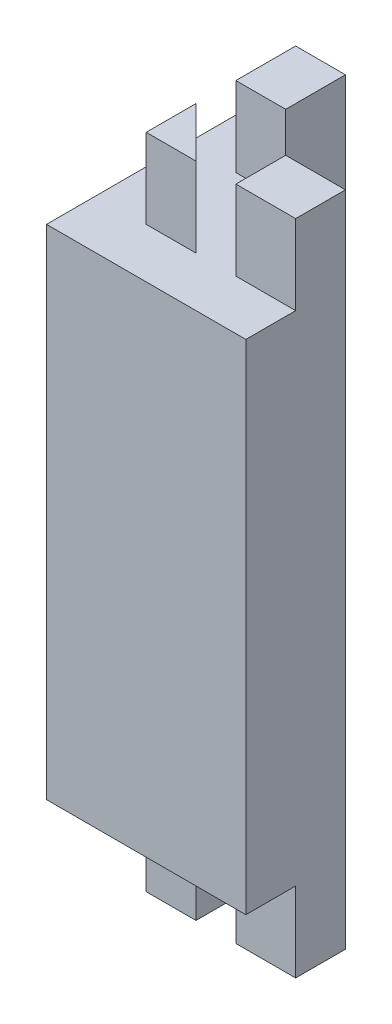
SolidWorks part; units mm, degrees
ref_plane "Front Plane" through (0, 0, 0) normal (0, 0, 1) x (1, 0, 0)
ref_plane "Top Plane" through (0, 0, 0) normal (0, 1, 0) x (1, 0, 0)
ref_plane "Right Plane" through (0, 0, 0) normal (1, 0, 0) x (0, 0, -1)
sketch "Sketch12" plane through (0, 0, 0) normal (0, 1, 0) x (1, 0, 0)
  line L0 (-5, -5) -> (5, -5)
  line L1 (-5, -5) -> (-5, 0)
  line L2 (0, 0) -> (5, 0)
  line L3 (5, -5) -> (5, 0)
  line L4 (-5, 0) -> (-5, 5)
  line L5 (-5, 5) -> (0, 5)
  line L6 (0, 0) -> (0, 5)
  dimension "D1" = 5
  dimension "D2" = 10
  dimension "D3" = 5
  dimension "D4" = 5
extrude "Boss-Extrude2" add sketch "Sketch12" along normal blind 25
sketch "Sketch13" plane through (0, 0, 0) normal (0, 1, 0) x (1, 0, 0)
  line L1 (0, 5) -> (-2.5, 5)
  line L2 (0, 5) -> (0, 2)
  line L3 (0, 2) -> (-2.5, 2)
  line L4 (-2.5, 5) -> (-2.5, 2)
  line L5 (5, 0) -> (2, 0)
  line L6 (5, 0) -> (5, -2.5)
  line L7 (5, -2.5) -> (2, -2.5)
  line L8 (2, 0) -> (2, -2.5)
  line L9 (0, 0) -> (-2.5, 0)
  line L10 (0, 0) -> (0, -2.5)
  line L11 (0, -2.5) -> (-2.5, -2.5)
  line L12 (-2.5, 0) -> (-2.5, -2.5)
  dimension "D1" = 2.5
  dimension "D2" = 3
  dimension "D3" = 3
  dimension "D4" = 2.5
extrude "Boss-Extrude3" add sketch "Sketch13" against normal blind 4
sketch "Sketch15" plane through (0, 25, 0) normal (0, 1, 0) x (1, 0, 0)
  line L0 (5, 0) -> (0, 0) construction
  line L1 (0, 5) -> (-2.5, 5)
  line L2 (0, 5) -> (0, 2)
  line L3 (0, 2) -> (-2.5, 2)
  line L4 (-2.5, 5) -> (-2.5, 2)
  line L5 (5, 0) -> (2, 0)
  line L6 (5, 0) -> (5, -2.5)
  line L7 (5, -2.5) -> (2, -2.5)
  line L8 (2, 0) -> (2, -2.5)
  line L11 (0, -2.5) -> (-2.5, -2.5)
  line L12 (-2.5, 0) -> (-2.5, -2.5)
  line L13 (5, -5) -> (5, 0) construction
  line L14 (-2.5, 0) -> (0, -2.5)
  dimension "D1" = 2.5
  dimension "D2" = 3
  dimension "D3" = 3
  dimension "D4" = 2.5
  dimension "D5" = 2.5
  dimension "D6" = 2.5
  dimension "D9" = 7.5
extrude "Boss-Extrude4" add sketch "Sketch15" along normal blind 4
